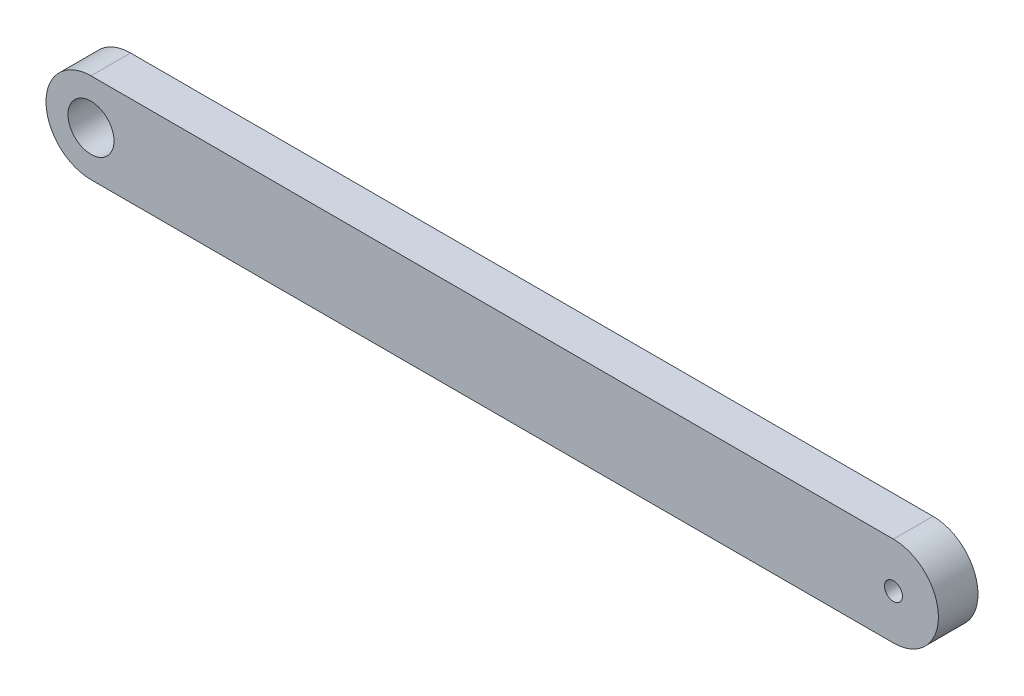
SolidWorks part; units mm, degrees
ref_plane "Front Plane" through (0, 0, 0) normal (0, 0, 1) x (1, 0, 0)
ref_plane "Top Plane" through (0, 0, 0) normal (0, 1, 0) x (1, 0, 0)
ref_plane "Right Plane" through (0, 0, 0) normal (1, 0, 0) x (0, 0, -1)
sketch "Sketch1" plane through (0, 0, 0) normal (0, 0, 1) x (1, 0, 0)
  line L0 (0, 0) -> (55.75, 0) construction
  line L1 (0, 3.125) -> (55.75, 3.125)
  line L2 (0, -3.125) -> (55.75, -3.125)
  arc A0 (0, 3.125) -> (0, -3.125) centre (0, 0) ccw
  arc A1 (55.75, -3.125) -> (55.75, 3.125) centre (55.75, 0) ccw
  circle A2 centre (0, 0) radius 1.6
  circle A3 centre (55.75, 0) radius 0.625
  point P3 (27.875, 0)
  dimension "D2" = 3.2
  dimension "D3" = 3.125
  dimension "D4" = 1.25
  dimension "D1" = 55.75
extrude "Boss-Extrude1" add sketch "Sketch1" along normal blind 2.75
